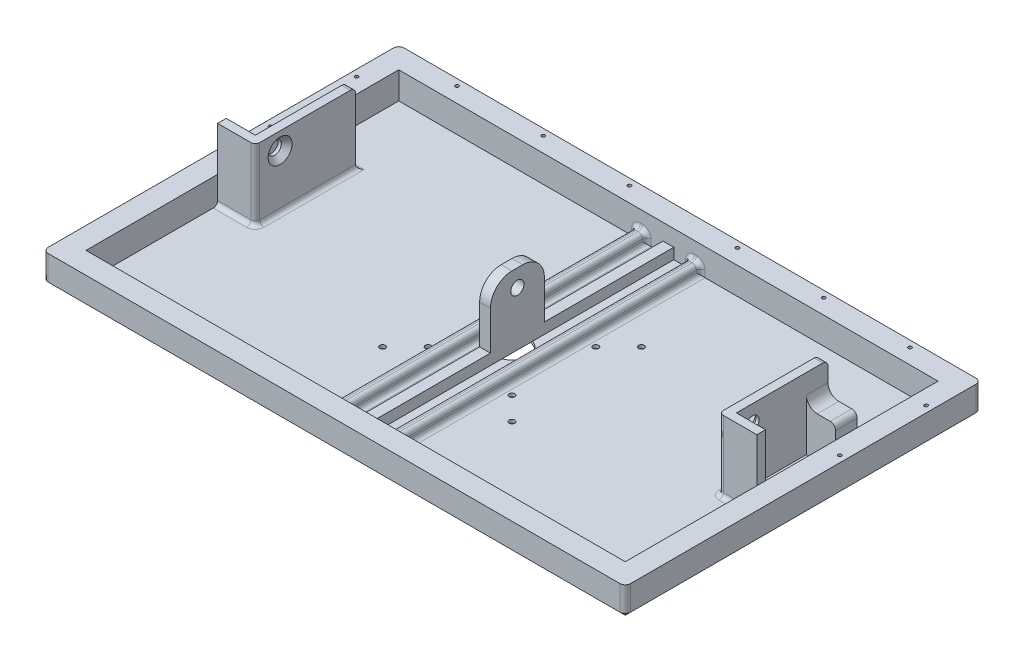
SolidWorks part; units mm, degrees
ref_plane "Front Plane" through (0, 0, 0) normal (0, 0, 1) x (1, 0, 0)
ref_plane "Top Plane" through (0, 0, 0) normal (0, 1, 0) x (1, 0, 0)
ref_plane "Right Plane" through (0, 0, 0) normal (1, 0, 0) x (0, 0, -1)
sketch "Sketch1" plane through (0, 0, 0) normal (0, 1, 0) x (1, 0, 0)
  line L1 (-270, -165) -> (270, -165)
  line L2 (-270, -165) -> (-270, 165)
  line L3 (-270, 165) -> (270, 165)
  line L4 (270, -165) -> (270, 165)
  line L5 (-270, -165) -> (270, 165) construction
  line L6 (-270, 165) -> (270, -165) construction
  point P0 (0, 0)
  dimension "D1" = 540
  dimension "D2" = 330
extrude "Boss-Extrude1" add sketch "Sketch1" along normal blind 3
sketch "Sketch2" plane through (0, 3, 0) normal (0, 1, 0) x (1, 0, 0)
  line L0 (250, 145) -> (-250, 145)
  line L1 (270, -165) -> (-270, -165)
  line L2 (270, -165) -> (270, 165)
  line L3 (270, 165) -> (-270, 165)
  line L4 (-270, -165) -> (-270, 165)
  line L5 (270, -165) -> (-270, 165) construction
  line L6 (270, 165) -> (-270, -165) construction
  line L7 (-250, -145) -> (-250, 145)
  line L8 (250, -145) -> (-250, -145)
  line L9 (250, -145) -> (250, 145)
  point P0 (0, 0)
  dimension "D1" = 20
  dimension "D2" = 540
extrude "Boss-Extrude2" add sketch "Sketch2" along normal blind 25 contours L0 L7 L8 L9 | L2 L1 L4 L3
fillet "Fillet1" radius 5 4 edges at (-270, 14, -165) (-270, 14, 165) (270, 14, 165) (270, 14, -165)
sketch "Sketch4" plane through (0, 28, 0) normal (0, 1, 0) x (1, 0, 0)
  line L0 (-270, 0) -> (-264, 0) construction
  line L1 (-270, -160) -> (-270, 160) construction
  line L2 (-264, 0) -> (-264, 40) construction
  line L3 (-264, 40) -> (-264, 120) construction
  line L4 (0, 0) -> (0, 145) construction
  line L5 (250, 145) -> (-250, 145) construction
  line L6 (0, 165) -> (0, 159) construction
  line L7 (265, 165) -> (-265, 165) construction
  line L8 (0, 159) -> (-50, 159) construction
  line L9 (-50, 159) -> (-130, 159) construction
  line L10 (-130, 159) -> (-210, 159) construction
  line L11 (130, 159) -> (210, 159) construction
  line L12 (50, 159) -> (130, 159) construction
  line L13 (264, 40) -> (264, 120) construction
  circle A0 centre (-264, 120) radius 1.6
  circle A1 centre (-264, 40) radius 1.6
  circle A2 centre (-210, 159) radius 1.6
  circle A3 centre (-130, 159) radius 1.6
  circle A4 centre (-50, 159) radius 1.6
  circle A5 centre (50, 159) radius 1.6
  circle A6 centre (130, 159) radius 1.6
  circle A7 centre (210, 159) radius 1.6
  circle A8 centre (264, 40) radius 1.6
  circle A9 centre (264, 120) radius 1.6
  dimension "D1" = 50
  dimension "D2" = 80
  dimension "D3" = 80
  dimension "D4" = 6
  dimension "D5" = 6
  dimension "D6" = 40
  dimension "D7" = 80
extrude "Cut-Extrude1" cut sketch "Sketch4" against normal up to surface (28 mm away) up to face at (0, 0, 0)
sketch "Sketch5" plane through (0, 3, 0) normal (0, 1, 0) x (1, 0, 0)
  circle A0 centre (0, 0) radius 15
  dimension "D1" = 30
extrude "Cut-Extrude2" cut sketch "Sketch5" against normal up to surface (3 mm away) up to face at (-264, 0, -41.6)
sketch "Sketch6" plane through (0, 3, 0) normal (0, 1, 0) x (1, 0, 0)
  line L0 (0, 145) -> (25, 145) construction
  line L1 (250, 145) -> (-250, 145) construction
  line L2 (25, 145) -> (25, -145) construction
  line L3 (250, -145) -> (-250, -145) construction
  line L4 (0, 145) -> (-25, 145) construction
  line L5 (250, 145) -> (-250, 145) construction
  line L6 (-25, 145) -> (-25, -145) construction
  line L7 (250, -145) -> (-250, -145) construction
  line L9 (20, -145) -> (30, -145)
  line L10 (20, -145) -> (20, 145)
  line L11 (20, 145) -> (30, 145)
  line L12 (30, -145) -> (30, 145)
  line L13 (20, -145) -> (30, 145) construction
  line L14 (20, 145) -> (30, -145) construction
  line L15 (-30, -145) -> (-20, -145)
  line L16 (-30, -145) -> (-30, 145)
  line L17 (-30, 145) -> (-20, 145)
  line L18 (-20, -145) -> (-20, 145)
  line L19 (-30, -145) -> (-20, 145) construction
  line L20 (-30, 145) -> (-20, -145) construction
  point P13 (25, 0)
  point P19 (-25, 0)
  dimension "D1" = 25
  dimension "D2" = 25
  dimension "D3" = 10
  dimension "D4" = 10
extrude "Boss-Extrude3" add sketch "Sketch6" along normal blind 10
fillet "Fillet3" radius 4 20 edges at (20, 8, 145) (30, 8, 145) (20, 8, -145) (30, 8, -145) (-30, 8, 145) (-20, 8, 145) (-20, 8, -145) (-30, 8, -145) (-20, 3, 0) (20, 3, 0) (25, 13, 145) (20, 13, 0) (25, 13, -145) (30, 13, 0) (-25, 13, 145) (-25, 13, -145) (-30, 3, 0) (-20, 13, 0) (-30, 13, 0) (30, 3, 0)
chamfer "Chamfer1" distance 5 angle 45 8 edges at (270, 0, 0) (0, 0, -165) (0, 0, 165) (268.5355, 0, -163.5355) (268.5355, 0, 163.5355) (-268.5355, 0, -163.5355) (-268.5355, 0, 163.5355) (-270, 0, 0)
sketch "Sketch7" plane through (0, 0, 0) normal (0, -1, 0) x (1, 0, 0)
  line L1 (-60, -60) -> (60, -60) construction
  line L2 (-60, -60) -> (-60, 60) construction
  line L3 (-60, 60) -> (60, 60) construction
  line L4 (60, -60) -> (60, 60) construction
  line L5 (-60, -60) -> (60, 60) construction
  line L6 (-60, 60) -> (60, -60) construction
  circle A0 centre (-60, 60) radius 2.6
  circle A1 centre (60, 60) radius 2.6
  circle A2 centre (60, -60) radius 2.6
  circle A3 centre (-60, -60) radius 2.6
  point P0 (0, 0)
  dimension "D1" = 120
  dimension "D2" = 120
extrude "Cut-Extrude3" cut sketch "Sketch7" against normal up to surface (3 mm away) up to face at (-142, 3, 0)
sketch "Sketch9" plane through (0, 0, 0) normal (0, -1, 0) x (1, 0, 0)
  line L1 (-38.8909, -38.8909) -> (38.8909, -38.8909) construction
  line L2 (-38.8909, -38.8909) -> (-38.8909, 38.8909) construction
  line L3 (-38.8909, 38.8909) -> (38.8909, 38.8909) construction
  line L4 (38.8909, -38.8909) -> (38.8909, 38.8909) construction
  line L5 (-38.8909, -38.8909) -> (38.8909, 38.8909) construction
  line L6 (-38.8909, 38.8909) -> (38.8909, -38.8909) construction
  circle A0 centre (-38.8909, 38.8909) radius 2.6
  circle A1 centre (38.8909, 38.8909) radius 2.6
  circle A2 centre (38.8909, -38.8909) radius 2.6
  circle A3 centre (-38.8909, -38.8909) radius 2.6
  point P0 (0, 0)
  dimension "D1" = 110
  dimension "D2" = 110
extrude "Cut-Extrude4" cut sketch "Sketch9" against normal blind 47
sketch "Sketch11" plane through (0, 3, 0) normal (0, 1, 0) x (1, 0, 0)
  line L0 (-250, 0) -> (-34, 0) construction
  line L1 (-250, -145) -> (-250, 145) construction
  line L2 (-34, -145) -> (-34, 145) construction
  line L3 (-250, 0) -> (-219, 0) construction
  line L5 (-223, 70) -> (-215, 70)
  line L6 (-223, 70) -> (-223, -70)
  line L7 (-223, -70) -> (-215, -70)
  line L8 (-215, 70) -> (-215, -70)
  line L9 (-223, 70) -> (-215, -70) construction
  line L10 (-223, -70) -> (-215, 70) construction
  dimension "D1" = 31
  dimension "D2" = 140
  dimension "D3" = 8
  dimension "D4" = 31
extrude "Boss-Extrude4" add sketch "Sketch11" along normal blind 66
sketch "Sketch12" plane through (-223, 0, 0) normal (-1, 0, 0) x (0, 0, 1)
  line L0 (0, 0) -> (0, 28) construction
  line L1 (160, 28) -> (-160, 28) construction
  line L2 (0, 28) -> (0, 53) construction
  circle A0 centre (0, 53) radius 6.1
  dimension "D2" = 12.2
  dimension "D1" = 25
extrude "Cut-Extrude5" cut sketch "Sketch12" against normal up to surface (8 mm away) up to face at (-215, 36, 0)
sketch "Sketch13" plane through (-223, 0, 0) normal (-1, 0, 0) x (0, 0, 1)
  line L0 (0, 0) -> (0, 69) construction
  line L1 (-70, 69) -> (70, 69) construction
  line L2 (0, 69) -> (15, 69) construction
  line L3 (160, 0) -> (-38.751, 0) construction
  line L4 (15, 69) -> (23, 69)
  line L5 (15, 69) -> (15, 0)
  line L6 (15, 0) -> (23, 0)
  line L7 (23, 69) -> (23, 0)
  line L8 (0, 0) -> (0, 53) construction
  line L9 (0, 53) -> (-50, 53) construction
  line L10 (-50, 53) -> (-50, 40.75) construction
  line L11 (-41.249, 0) -> (-118.751, 0) construction
  line L12 (-50, 40.75) -> (-70, 40.75)
  line L13 (-50, 40.75) -> (-50, 0)
  line L14 (-50, 0) -> (-70, 0)
  line L15 (-70, 40.75) -> (-70, 0)
  dimension "D1" = 15
  dimension "D2" = 8
  dimension "D3" = 12.25
  dimension "D4" = 50
  dimension "D5" = 20
extrude "Boss-Extrude5" add sketch "Sketch13" along normal up to surface (27 mm away) up to face at (-250, 15.5, 0)
sketch "Sketch15" plane through (0, 69, 0) normal (0, 1, 0) x (1, 0, 0)
  line L0 (-250, -23) -> (-223, -23) construction
  line L1 (-215, -70) -> (-223, -70)
  line L2 (-215, -70) -> (-215, -23)
  line L3 (-215, -23) -> (-223, -23)
  line L4 (-223, -70) -> (-223, -23)
  line L5 (-223, -23) -> (-223, -70) construction
extrude "Cut-Extrude6" cut sketch "Sketch15" against normal up to surface (66 mm away) up to face at (-60, 3, 57.4)
fillet "Fillet4" radius 4 4 edges at (-215, 3, -23.5) (-232.5, 3, -70) (-232.5, 3, 23) (-215, 36, 23)
fillet "Fillet5" radius 10 1 edges at (-223, 40.75, -60)
fillet "Fillet6" radius 5 1 edges at (-250, 40.75, -60)
fillet "Fillet7" radius 5 1 edges at (-219, 69, -70)
chamfer "Chamfer2" distance 5 angle 45 1 edges at (-215, 53, 6.1)
sketch "Sketch16" plane through (0, 28, 0) normal (0, 1, 0) x (1, 0, 0)
  line L0 (-250, 145) -> (-250, 70) construction
  line L1 (-250, -145) -> (250, -145)
  line L2 (-250, -145) -> (-250, -23)
  line L3 (-250, 145) -> (250, 145)
  line L4 (250, -145) -> (250, 145)
  line L5 (-250, -145) -> (250, 145) construction
  line L6 (-250, 145) -> (250, -145) construction
  line L7 (-250, 70) -> (-215, 70)
  line L8 (-215, 70) -> (-215, -23)
  line L9 (-215, -23) -> (-250, -23)
  line L10 (-250, 70) -> (-250, 145)
  point P0 (0, 0)
  point P12 (-232.5, -23)
  dimension "D1" = 290
  dimension "D2" = 500
  dimension "D3" = 93
  dimension "D4" = 35
  dimension "D5" = 168
  dimension "D6" = 75
sketch "Sketch17" plane through (0, 28, 0) normal (0, 1, 0) x (1, 0, 0)
  line L0 (0, 0) -> (0, 165) construction
  line L1 (265, 165) -> (-265, 165) construction
ref_plane "Plane1" through (0, 0, 0) normal (1, 0, 0) x (0, 0, -1)
mirror "Mirror9" about plane through (0, 0, 0) normal (1, 0, 0) of bodies 111
sketch "Sketch19" plane through (0, 3, 0) normal (0, 1, 0) x (1, 0, 0)
  line L0 (250, 145) -> (-250, 145) construction
  line L1 (-5, -145) -> (5, -145)
  line L2 (-5, -145) -> (-5, 145)
  line L3 (-5, 145) -> (5, 145)
  line L4 (5, -145) -> (5, 145)
  line L5 (-5, -145) -> (5, 145) construction
  line L6 (-5, 145) -> (5, -145) construction
  point P0 (0, 0)
  dimension "D1" = 10
extrude "Boss-Extrude6" add sketch "Sketch19" along normal up to surface (10 mm away) up to face at (-25, 13, 0)
sketch "Sketch20" plane through (0, 13, 0) normal (0, 1, 0) x (1, 0, 0)
  line L0 (5, 14.1421) -> (5, 145) construction
  line L1 (-5, -25) -> (5, -25)
  line L2 (-5, -25) -> (-5, 25)
  line L3 (-5, 25) -> (5, 25)
  line L4 (5, -25) -> (5, 25)
  line L5 (-5, -25) -> (5, 25) construction
  line L6 (-5, 25) -> (5, -25) construction
  point P0 (0, 0)
  dimension "D1" = 50
extrude "Boss-Extrude7" add sketch "Sketch20" along normal up to surface (56 mm away) up to face at (-227.7388, 69, -4.8817)
fillet "Fillet8" radius 20 2 edges at (0, 69, -25) (0, 69, 25)
sketch "Sketch21" plane through (-5, 0, 0) normal (-1, 0, 0) x (0, 0, 1)
  circle A0 centre (0, 53) radius 6.1
extrude "Cut-Extrude7" cut sketch "Sketch21" against normal up to surface (10 mm away) up to face at (5, 25.6904, 0)
